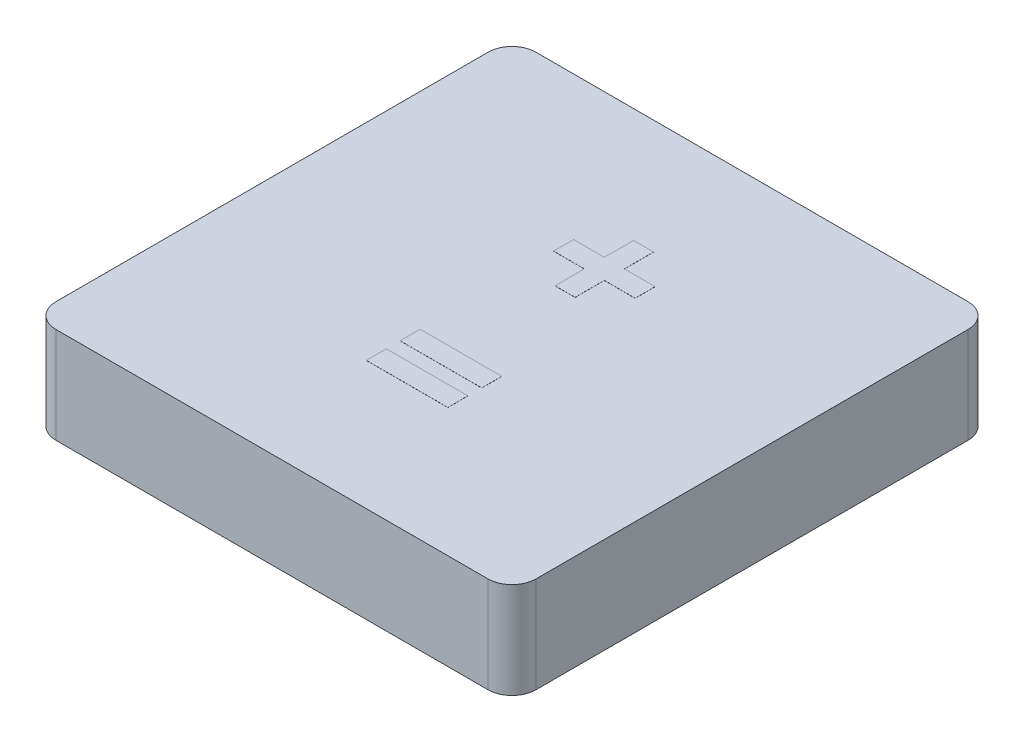
SolidWorks part; units mm, degrees
ref_plane "Front Plane" through (0, 0, 0) normal (0, 0, 1) x (1, 0, 0)
ref_plane "Top Plane" through (0, 0, 0) normal (0, 1, 0) x (1, 0, 0)
ref_plane "Right Plane" through (0, 0, 0) normal (1, 0, 0) x (0, 0, -1)
sketch "Sketch1" plane through (0, 0, 0) normal (0, 1, 0) x (1, 0, 0)
  line L0 (0, 0) -> (12.7, 0)
  line L1 (12.7, 0) -> (12.7, 12.7)
  line L2 (12.7, 12.7) -> (0, 12.7)
  line L3 (0, 12.7) -> (0, 0)
  dimension "D1" = 12.7
  dimension "D2" = 12.7
extrude "Boss-Extrude1" add sketch "Sketch1" along normal blind 2.54
fillet "Fillet1" radius 0.635 4 edges at (0, 1.27, -12.7) (12.7, 1.27, -12.7) (12.7, 1.27, 0) (0, 1.27, 0)
shell "Shell1" thickness 0.635 removed face at (6.35, 0, -6.35)
sketch "Sketch2" plane through (0, 1.905, 0) normal (0, -1, 0) x (-1, 0, 0)
  line L0 (-0.635, 6.35) -> (-12.065, 6.35) construction
  line L1 (-0.635, 12.065) -> (-0.635, 0.635) construction
  line L2 (-12.065, 0.635) -> (-12.065, 12.065) construction
  line L3 (-6.35, 0.635) -> (-6.35, 12.065) construction
  line L4 (-0.635, 0.635) -> (-12.065, 0.635) construction
  line L5 (-12.065, 12.065) -> (-0.635, 12.065) construction
  circle A0 centre (-6.35, 6.35) radius 2.54
  dimension "D1" = 5.08
extrude "Boss-Extrude2" add sketch "Sketch2" along normal up to surface (1.905 mm away) up to face at (6.35, 0, -6.35)
sketch "Sketch3" plane through (0, 2.54, 0) normal (0, 1, 0) x (1, 0, 0)
  line L0 (0.635, 0) -> (12.065, 0) construction
  line L1 (0, 12.065) -> (0, 0.635) construction
  line L2 (12.065, 12.7) -> (0.635, 12.7) construction
  text T0 "<b>+</b>"
  text T1 "<b>=</b>"
  dimension "D1" = 2.54
  dimension "D2" = 5.207
  dimension "D3" = 5.588
  dimension "D4" = 5.1816
extrude "Boss-Extrude3" add sketch "Sketch3" along normal blind 0.0025
